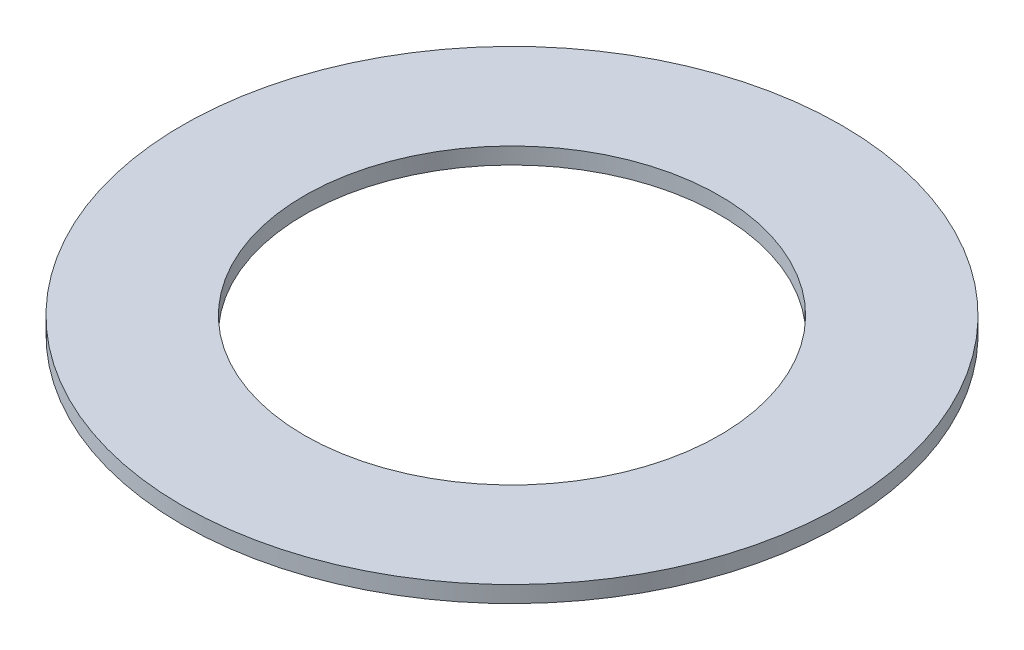
SolidWorks part; units mm, degrees
ref_plane "Front Plane" through (0, 0, 0) normal (0, 0, 1) x (1, 0, 0)
ref_plane "Top Plane" through (0, 0, 0) normal (0, 1, 0) x (1, 0, 0)
ref_plane "Right Plane" through (0, 0, 0) normal (1, 0, 0) x (0, 0, -1)
sketch "Sketch1" plane through (0, 0, 0) normal (0, 1, 0) x (1, 0, 0)
  circle A0 centre (0, 0) radius 63.5
  dimension "D1" = 127
extrude "Boss-Extrude1" add sketch "Sketch1" along normal blind 3.18
sketch "Sketch2" plane through (0, 3.18, 0) normal (0, 1, 0) x (1, 0, 0)
  circle A0 centre (0, 0) radius 40.005
  dimension "D1" = 80.01
extrude "Cut-Extrude1" cut sketch "Sketch2" against normal blind 3.18
equation "\"ODia\"= 5in"
equation "\"IDia\"= 3.15in"
equation "\"Thick\"= .125in"
